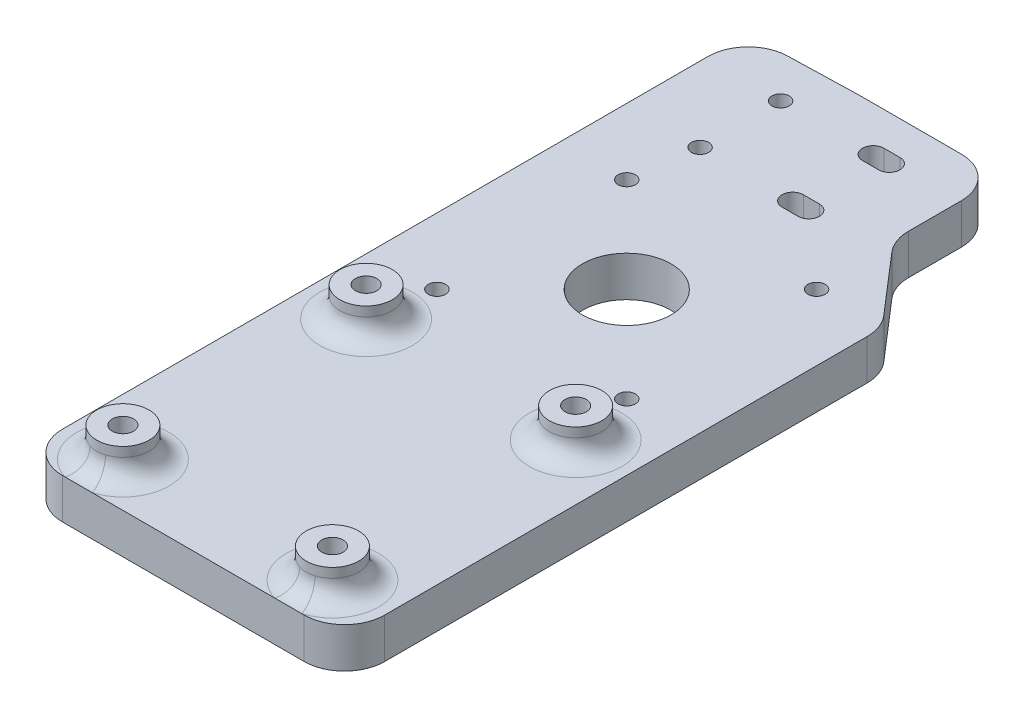
SolidWorks part; units mm, degrees
ref_plane "Alzado" through (0, 0, 0) normal (0, 0, 1) x (1, 0, 0)
ref_plane "Planta" through (0, 0, 0) normal (0, 1, 0) x (1, 0, 0)
ref_plane "Vista lateral" through (0, 0, 0) normal (1, 0, 0) x (0, 0, -1)
sketch "Croquis1" plane through (0, 0, 0) normal (0, 1, 0) x (1, 0, 0)
  line L0 (12.4888, 90.7353) -> (-12.4888, 90.7353)
  line L1 (-12.4888, 90.7353) -> (12.4888, 90.7353)
  line L2 (-40, 39.8326) -> (-40, -80)
  line L3 (-30, -90) -> (30, -90)
  line L4 (40, 39.8326) -> (40, -80)
  line L6 (0, -49) -> (-4.6306, -49) construction
  line L9 (0, 0) -> (0, -51.3503) construction
  line L10 (-40, 39.8326) -> (-40, 80.2637)
  line L11 (-30.2672, 90.2601) -> (-12.4888, 90.7353)
  line L12 (22.4888, 80.7353) -> (22.4888, 67.5648)
  line L13 (24.9172, 61.0325) -> (37.5716, 46.365)
  arc A2 (-13.023, 90.7211) -> (-12.4888, 90.7353) centre (-12.4888, 80.7353) cw
  arc A12 (-40, -80) -> (-30, -90) centre (-30, -80) ccw
  arc A13 (40, -80) -> (30, -90) centre (30, -80) cw
  arc A14 (22.4888, 80.7353) -> (12.4888, 90.7353) centre (12.4888, 80.7353) ccw
  arc A15 (22.4888, 67.5648) -> (24.9172, 61.0325) centre (32.4888, 67.5648) ccw
  arc A16 (37.5716, 46.365) -> (40, 39.8326) centre (30, 39.8326) cw
  arc A17 (-30.2672, 90.2601) -> (-40, 80.2637) centre (-30, 80.2637) ccw
  point P0 (0, 0)
  point P15 (-22.4888, 90.7353)
  point P26 (-40, -90)
  point P29 (40, -90)
  dimension "D1" = 10
  dimension "D3" = 80
extrude "Saliente-Extruir1" add sketch "Croquis1" along normal blind 10 contours A2 L2 L3 L4 L0 region at (-1.4705, 0, 3.0627)
sketch "Croquis2" plane through (0, 0, 0) normal (0, -1, 0) x (1, 0, 0)
  line L0 (-30, 90) -> (30, 90) construction
  line L1 (0, 0) -> (0, 18.1232) construction
  line L2 (-26.0188, 48.8) -> (-13.5394, 48.8) construction
  circle A0 centre (-26.0188, 79) radius 6.5
  circle A1 centre (-26.0188, 79) radius 2.65
  circle A2 centre (-26.0188, 18.6) radius 2.65
  circle A3 centre (-26.0188, 18.6) radius 6.5
  circle A4 centre (26.0188, 79) radius 2.65
  circle A5 centre (26.0188, 79) radius 6.5
  circle A6 centre (26.0188, 18.6) radius 6.5
  circle A7 centre (26.0188, 18.6) radius 2.65
  dimension "D2" = 13
  dimension "D3" = 5.3
  dimension "D1" = 11
  dimension "D4" = 30.2
extrude "Saliente-Extruir2" add sketch "Croquis2" against normal blind 7.35 from surface starting at face at (5.9415, 10, -23.6486)
sketch "Croquis3" plane through (0, 0, 0) normal (0, -1, 0) x (1, 0, 0)
  circle A0 centre (-26.0188, 79) radius 2.65
  circle A1 centre (-26.0188, 18.6) radius 2.65
  circle A2 centre (26.0188, 18.6) radius 2.65
  circle A3 centre (26.0188, 79) radius 2.65
extrude "Cortar-Extruir1" cut sketch "Croquis3" against normal blind 68 and the other way blind 46
sketch "Croquis4" plane through (0, 0, 0) normal (0, -1, 0) x (1, 0, 0)
  line L0 (0, 0) -> (0, -20.1076) construction
  line L1 (0, -20.1076) -> (-7.7372, -20.1076) construction
  circle A0 centre (-23.57, -43.6776) radius 2.15
  circle A1 centre (-23.57, 3.4624) radius 2.15
  circle A2 centre (23.57, 3.4624) radius 2.15
  circle A3 centre (23.57, -43.6776) radius 2.15
  circle A4 centre (0, -20.1076) radius 11
  dimension "D1" = 4.3
  dimension "D4" = 22
  dimension "D2" = 23.57
  dimension "D3" = 23.57
extrude "Cortar-Extruir2" cut sketch "Croquis4" against normal blind 32 and the other way blind 37
sketch "Croquis6" plane through (0, 10, 0) normal (0, 1, 0) x (1, 0, 0)
  line L0 (-23.57, 43.6776) -> (-23.57, 59.7353) construction
  line L1 (1.58, 79.7353) -> (5.58, 79.7353) construction
  line L2 (-24.1067, 69.7353) -> (-27.2294, 69.7353) construction
  line L3 (1.58, 82.3889) -> (5.58, 82.3889)
  line L6 (1.58, 77.0818) -> (5.58, 77.0818)
  line L9 (0, 0) -> (0, 19.1883) construction
  line L10 (1.58, 59.7353) -> (5.58, 59.7353) construction
  line L11 (1.58, 57.0818) -> (5.58, 57.0818)
  line L12 (1.58, 62.3889) -> (5.58, 62.3889)
  circle A9 centre (-21.42, 59.7353) radius 2.15
  circle A10 centre (-21.42, 79.7353) radius 2.15
  arc A11 (1.58, 82.3889) -> (1.58, 77.0818) centre (1.58, 79.7353) ccw
  arc A12 (5.58, 77.0818) -> (5.58, 82.3889) centre (5.58, 79.7353) ccw
  arc A13 (1.58, 57.0818) -> (1.58, 62.3889) centre (1.58, 59.7353) cw
  arc A14 (5.58, 62.3889) -> (5.58, 57.0818) centre (5.58, 59.7353) cw
  point P4 (3.58, 79.7353)
  point P13 (3.58, 59.7353)
extrude "Cortar-Extruir3" cut sketch "Croquis6" against normal blind 28 contours A9 | A10 | L6 A12 L3 A11 | L11 A14 L12 A13
fillet "Redondeo4" radius 5 4 edges at (26.0188, 10, 85.5) (-26.0188, 10, 85.5) (26.0188, 10, 25.1) (-26.0188, 10, 25.1)
hole_wizard "Refrentado para tornillo con cabeza troncocónica de M51" positions "Croquis8" profile "Croquis9" counterbore size "M5" standard "Ansi Metric" end condition through all
sketch "Croquis8" plane through (0, 0, 0) normal (0, -1, 0) x (-1, 0, 0)
  point P0 (-26.0188, -18.6)
  point P3 (-26.0188, -79)
  point P6 (26.0188, -79)
  point P9 (26.0188, -18.6)
sketch "Croquis9" plane through (26.0188, 0, 18.6) normal (1, 0, 0) x (0, 0, -1)
  line L0 (0, 0) -> (0, 17.35)
  line L1 (0, 17.35) -> (2.65, 17.35)
  line L3 (2.65, 17.35) -> (2.65, 3.7)
  line L4 (2.65, 3.7) -> (5.5, 3.7)
  line L5 (5.5, 3.7) -> (5.5, 0)
  line L7 (5.5, 0) -> (0, 0)
  line L11 (0, -6.35) -> (0, 107.95) construction
  dimension "Diámetro de taladro hasta el siguiente" = 5.3
  dimension "Profundidad de taladro hasta el siguiente" = 17.35
  dimension "Diámetro de refrentado" = 11
  dimension "Profundidad de refrentado" = 3.7
sketch "Croquis10" plane through (0, 10, 0) normal (0, 1, 0) x (1, 0, 0)
  line L0 (26.0188, -79) -> (26.0188, -81.65) construction
  line L1 (31.4125, -79) -> (31.4125, -81.65)
  line L2 (20.6251, -79) -> (20.6251, -81.65)
  circle A0 centre (26.0188, -79) radius 2.65 construction
  arc A1 (31.4125, -79) -> (20.6251, -79) centre (26.0188, -79) ccw
  arc A2 (20.6251, -81.65) -> (31.4125, -81.65) centre (26.0188, -81.65) ccw
  point P5 (26.0188, -80.325)
sketch "Croquis11" plane through (0, 0, 0) normal (0, -1, 0) x (1, 0, 0)
  line L0 (-21.9074, 36.8687) -> (-23.58, 38.144)
  line L1 (-23.58, 38.144) -> (-25.3708, 38.1161)
  line L2 (-28.4834, 53.6237) -> (-28.4834, 55.7006)
  line L3 (-28.4834, 55.7006) -> (-27.7447, 55.7006)
  line L4 (-27.7447, 55.7006) -> (-27.0061, 55.7006)
  line L5 (-27.0061, 55.7006) -> (-27.0061, 53.7308)
  line L6 (-24.4708, 50.8261) -> (-22.9433, 50.8991)
  line L7 (-22.9433, 50.8991) -> (-22.8728, 53.2999)
  line L8 (-22.8728, 53.2999) -> (-22.8023, 55.7006)
  line L9 (-22.8023, 55.7006) -> (-22.0725, 55.7006)
  line L10 (-22.0725, 55.7006) -> (-21.3428, 55.7006)
  line L11 (-21.3428, 55.7006) -> (-21.3428, 52.7424)
  line L12 (-21.3428, 52.7424) -> (-21.3428, 49.7841)
  line L13 (-21.3428, 49.7841) -> (-20.5425, 49.0561)
  line L14 (6.5529, 37.0872) -> (5.5861, 38.1856)
  line L15 (5.5861, 38.1856) -> (3.7489, 36.4168)
  line L16 (3.7085, 44.472) -> (5.4924, 42.7233)
  line L17 (5.4924, 42.7233) -> (7.2941, 44.472)
  line L18 (24.7134, 51.5147) -> (22.9786, 51.5147)
  line L19 (22.9786, 51.5147) -> (22.9786, 52.2534)
  line L20 (22.9786, 52.2534) -> (22.9786, 52.9921)
  line L21 (22.9786, 52.9921) -> (24.5962, 52.9921)
  line L22 (24.2098, 54.1001) -> (22.363, 54.1001)
  line L23 (22.363, 54.1001) -> (22.363, 52.4996)
  line L24 (22.363, 52.4996) -> (22.363, 50.8991)
  line L25 (22.363, 50.8991) -> (24.2713, 50.8272)
  line L26 (24.2713, 50.8272) -> (26.1795, 50.7553)
  line L27 (26.1795, 50.7553) -> (26.1795, 50.027)
  line L28 (26.1795, 50.027) -> (26.1795, 49.2986)
  line L29 (26.1795, 49.2986) -> (24.3206, 49.2986)
  line L30 (13.8681, 50.027) -> (13.8681, 50.7553)
  line L31 (13.8681, 50.7553) -> (15.7763, 50.8272)
  line L32 (15.7763, 50.8272) -> (17.6846, 50.8991)
  line L33 (17.6846, 50.8991) -> (17.7551, 53.2999)
  line L34 (17.7551, 53.2999) -> (17.8256, 55.7006)
  line L35 (17.8256, 55.7006) -> (18.5553, 55.7006)
  line L36 (18.5553, 55.7006) -> (19.2851, 55.7006)
  line L37 (19.2851, 55.7006) -> (19.2851, 53.0099)
  line L38 (15.9278, 49.2986) -> (13.8681, 49.2986)
  line L39 (13.8681, 49.2986) -> (13.8681, 50.027)
  line L40 (7.2199, 50.0373) -> (7.2199, 50.776)
  line L41 (7.2199, 50.776) -> (9.0174, 50.776)
  line L42 (11.4058, 53.5338) -> (11.4058, 55.7006)
  line L43 (11.4058, 55.7006) -> (12.1669, 55.7006)
  line L44 (12.1669, 55.7006) -> (12.928, 55.7006)
  line L45 (12.928, 55.7006) -> (12.844, 53.0934)
  line L46 (9.2991, 49.2986) -> (7.2199, 49.2986)
  line L47 (7.2199, 49.2986) -> (7.2199, 50.0373)
  line L48 (2.4072, 53.4845) -> (4.2651, 53.4845)
  line L49 (4.2651, 53.4845) -> (4.2651, 52.7458)
  line L50 (4.2651, 52.7458) -> (4.2651, 52.0072)
  line L51 (4.2651, 52.0072) -> (2.5244, 52.0072)
  line L52 (2.7877, 50.8991) -> (4.6345, 50.8991)
  line L53 (4.6345, 50.8991) -> (4.6345, 52.4996)
  line L54 (4.6345, 52.4996) -> (4.6345, 54.1001)
  line L55 (4.6345, 54.1001) -> (2.9724, 54.1729)
  line L56 (2.9724, 54.1729) -> (1.3104, 54.2457)
  line L57 (1.3104, 54.2457) -> (1.3104, 54.9992)
  line L58 (1.3104, 54.9992) -> (1.3104, 55.7527)
  line L59 (1.3104, 55.7527) -> (3.3043, 55.6622)
  line L60 (-7.3077, 50.027) -> (-7.3077, 50.7553)
  line L61 (-7.3077, 50.7553) -> (-5.3994, 50.8272)
  line L62 (-5.3994, 50.8272) -> (-3.4911, 50.8991)
  line L63 (-3.4911, 50.8991) -> (-3.4207, 53.2999)
  line L64 (-3.4207, 53.2999) -> (-3.3502, 55.7006)
  line L65 (-3.3502, 55.7006) -> (-2.6204, 55.7006)
  line L66 (-2.6204, 55.7006) -> (-1.8906, 55.7006)
  line L67 (-1.8906, 55.7006) -> (-1.8906, 53.0099)
  line L68 (-5.2479, 49.2986) -> (-7.3077, 49.2986)
  line L69 (-7.3077, 49.2986) -> (-7.3077, 50.027)
  line L70 (-10.6206, 51.5147) -> (-12.4785, 51.5147)
  line L71 (-12.4785, 51.5147) -> (-12.4785, 52.2534)
  line L72 (-12.4785, 52.2534) -> (-12.4785, 52.9921)
  line L73 (-12.4785, 52.9921) -> (-10.7378, 52.9921)
  line L74 (-10.8694, 50.776) -> (-9.0313, 50.776)
  line L75 (-9.0313, 50.776) -> (-9.0313, 50.0373)
  line L76 (-9.0313, 50.0373) -> (-9.0313, 49.2986)
  line L77 (-9.0313, 49.2986) -> (-11.1355, 49.2986)
  line L78 (-19.8654, 52.4996) -> (-19.8654, 55.7006)
  line L79 (-19.8654, 55.7006) -> (-19.1267, 55.7006)
  line L80 (-19.1267, 55.7006) -> (-18.388, 55.7006)
  line L81 (-18.388, 55.7006) -> (-18.388, 52.4996)
  line L82 (-18.388, 52.4996) -> (-18.388, 49.2986)
  line L83 (-18.388, 49.2986) -> (-19.1267, 49.2986)
  line L84 (-19.1267, 49.2986) -> (-19.8654, 49.2986)
  line L85 (-19.8654, 49.2986) -> (-19.8654, 52.4996)
  line L86 (35.5363, 51.5058) -> (35.5363, 54.2232)
  line L87 (35.5363, 54.2232) -> (32.8277, 54.2232)
  line L88 (32.8277, 54.2232) -> (30.1192, 54.2232)
  line L89 (30.1192, 54.2232) -> (30.1192, 53.5338)
  line L90 (32.7539, 52.2534) -> (34.7976, 52.2534)
  line L91 (34.7976, 52.2534) -> (34.7976, 51.5425)
  line L92 (33.1356, 48.8588) -> (35.5363, 48.7883)
  line L93 (35.5363, 48.7883) -> (35.5363, 51.5058)
  arc A0 (-21.7929, 32.6977) -> (-21.8352, 32.5543) centre (-21.5714, 32.5543) ccw
  arc A1 (-21.5762, 33.0144) -> (-21.7929, 32.6977) centre (-15.4233, 28.5729) ccw
  arc A2 (-21.2912, 33.3841) -> (-21.5762, 33.0144) centre (-15.5733, 28.6812) ccw
  arc A3 (-20.9535, 33.7758) -> (-21.2912, 33.3841) centre (-12.6842, 26.305) ccw
  arc A4 (-20.9535, 33.7758) -> (-20.6219, 34.1803) centre (-24.9909, 37.4233) ccw
  arc A5 (-20.6219, 34.1803) -> (-20.3547, 34.5887) centre (-23.9371, 36.6411) ccw
  arc A6 (-20.3547, 34.5887) -> (-20.1765, 34.9489) centre (-23.2212, 36.2309) ccw
  arc A7 (-20.1765, 34.9489) -> (-20.1533, 35.1726) centre (-20.5331, 35.099) ccw
  arc A8 (-20.1533, 35.1726) -> (-20.2693, 35.4017) centre (-20.6135, 35.0834) ccw
  arc A9 (-20.2693, 35.4017) -> (-20.7022, 35.8444) centre (-28.3805, 27.9036) ccw
  arc A10 (-20.7022, 35.8444) -> (-21.2608, 36.3495) centre (-28.5249, 27.7542) ccw
  arc A11 (-21.2608, 36.3495) -> (-21.9074, 36.8687) centre (-31.9176, 23.7397) ccw
  arc A12 (-25.3708, 38.1161) -> (-26.6444, 38.0299) centre (-25.1791, 25.8317) ccw
  arc A13 (-26.6444, 38.0299) -> (-27.5051, 37.7963) centre (-26.2775, 34.9755) ccw
  arc A14 (-27.5051, 37.7963) -> (-28.3226, 37.3077) centre (-26.0188, 34.3811) ccw
  arc A15 (-28.3226, 37.3077) -> (-29.4886, 36.3239) centre (-14.4056, 19.6288) ccw
  arc A16 (-29.4886, 36.3239) -> (-29.8579, 35.9562) centre (-25.8949, 32.3461) ccw
  arc A17 (-29.8579, 35.9562) -> (-30.1699, 35.572) centre (-26.6312, 33.0169) ccw
  arc A18 (-30.1699, 35.572) -> (-30.3922, 35.2229) centre (-27.2951, 33.4962) ccw
  arc A19 (-30.3922, 35.2229) -> (-30.4533, 34.988) centre (-29.971, 34.988) ccw
  arc A20 (-30.4533, 34.988) -> (-30.3913, 34.7523) centre (-29.9738, 34.988) ccw
  arc A21 (-30.3913, 34.7523) -> (-30.164, 34.3986) centre (-27.2015, 36.5531) ccw
  arc A22 (-30.164, 34.3986) -> (-29.8454, 34.0085) centre (-26.5246, 37.0454) ccw
  arc A23 (-29.8454, 34.0085) -> (-29.4684, 33.6338) centre (-25.7278, 37.7741) ccw
  arc A24 (-29.0911, 33.2766) -> (-29.4684, 33.6338) centre (-36.9497, 25.3528) ccw
  arc A25 (-28.7728, 32.9395) -> (-29.0911, 33.2766) centre (-34.0818, 28.2444) ccw
  arc A26 (-28.5286, 32.6491) -> (-28.7728, 32.9395) centre (-34.416, 27.9489) ccw
  arc A27 (-28.4834, 32.52) -> (-28.5286, 32.6491) centre (-28.6902, 32.52) ccw
  arc A28 (-28.6329, 32.4158) -> (-28.4834, 32.52) centre (-28.5945, 32.52) ccw
  arc A29 (-29.1844, 32.6662) -> (-28.6329, 32.4158) centre (-27.1979, 36.3089) ccw
  arc A30 (-29.8159, 33.0694) -> (-29.1844, 32.6662) centre (-26.5815, 37.4392) ccw
  arc A31 (-30.3073, 33.5147) -> (-29.8159, 33.0694) centre (-27.8204, 35.7654) ccw
  arc A32 (-30.3073, 33.5147) -> (-30.5256, 33.7128) centre (-31.4223, 32.5057) ccw
  arc A33 (-30.5256, 33.7128) -> (-30.7934, 33.8803) centre (-31.7051, 32.125) ccw
  arc A34 (-30.7934, 33.8803) -> (-31.0678, 33.9951) centre (-31.621, 32.2869) ccw
  arc A35 (-31.0678, 33.9951) -> (-31.304, 34.0324) centre (-31.304, 33.2657) ccw
  arc A36 (-31.7288, 34.1047) -> (-31.304, 34.0324) centre (-31.304, 35.3167) ccw
  arc A37 (-32.0923, 34.3129) -> (-31.7288, 34.1047) centre (-31.3483, 35.1904) ccw
  arc A38 (-32.3366, 34.6215) -> (-32.0923, 34.3129) centre (-31.4448, 35.0766) ccw
  arc A39 (-32.4231, 34.9813) -> (-32.3366, 34.6215) centre (-31.6316, 34.9813) ccw
  arc A40 (-32.4231, 34.9813) -> (-32.4814, 35.1754) centre (-32.7757, 34.9813) ccw
  arc A41 (-32.4814, 35.1754) -> (-32.7305, 35.5219) centre (-36.8916, 32.2669) ccw
  arc A42 (-32.7305, 35.5219) -> (-33.0689, 35.9177) centre (-37.4441, 31.8347) ccw
  arc A43 (-33.0689, 35.9177) -> (-33.4696, 36.3191) centre (-39.2224, 30.1753) ccw
  arc A44 (-34.2263, 37.1004) -> (-33.4696, 36.3191) centre (-25.8639, 44.4417) ccw
  arc A45 (-34.1987, 37.4176) -> (-34.2263, 37.1004) centre (-34.0606, 37.2458) ccw
  arc A46 (-33.8228, 37.4345) -> (-34.1987, 37.4176) centre (-33.9992, 37.1694) ccw
  arc A47 (-32.9118, 36.7675) -> (-33.8228, 37.4345) centre (-40.787, 26.9679) ccw
  arc A48 (-32.9118, 36.7675) -> (-32.5122, 36.4746) centre (-29.4133, 41.1209) ccw
  arc A49 (-32.5122, 36.4746) -> (-32.0991, 36.227) centre (-29.7454, 40.6231) ccw
  arc A50 (-32.0991, 36.227) -> (-31.7278, 36.0511) centre (-30.1248, 39.9144) ccw
  arc A51 (-31.7278, 36.0511) -> (-31.4825, 36.0022) centre (-31.4825, 36.6421) ccw
  arc A52 (-31.4825, 36.0022) -> (-31.0911, 36.1465) centre (-31.4825, 36.6052) ccw
  arc A53 (-31.0911, 36.1465) -> (-30.4077, 36.7828) centre (-38.1198, 44.3825) ccw
  arc A54 (-30.4077, 36.7828) -> (-29.5542, 37.7226) centre (-41.4864, 47.7001) ccw
  arc A55 (-29.5542, 37.7226) -> (-28.5152, 39.0134) centre (-63.5871, 66.1803) ccw
  arc A56 (-28.5152, 39.0134) -> (-28.3768, 39.2937) centre (-29.1364, 39.4946) ccw
  arc A57 (-28.3768, 39.2937) -> (-28.274, 39.786) centre (-32.9762, 40.5102) ccw
  arc A58 (-28.274, 39.786) -> (-28.2072, 40.4153) centre (-34.938, 40.8123) ccw
  arc A59 (-28.2072, 40.4153) -> (-28.1854, 41.1551) centre (-40.7482, 41.1551) ccw
  arc A60 (-28.1854, 41.1551) -> (-28.2106, 42.0676) centre (-44.6696, 41.1551) ccw
  arc A61 (-28.2106, 42.0676) -> (-28.2961, 42.6915) centre (-32.1105, 41.8514) ccw
  arc A62 (-28.2961, 42.6915) -> (-28.4633, 43.191) centre (-30.7199, 42.1577) ccw
  arc A63 (-28.4633, 43.191) -> (-28.7424, 43.684) centre (-31.4758, 41.8116) ccw
  arc A64 (-28.7424, 43.684) -> (-29.4471, 44.613) centre (-38.6834, 36.8741) ccw
  arc A65 (-29.4471, 44.613) -> (-30.2534, 45.4912) centre (-39.5355, 36.1601) ccw
  arc A66 (-30.2534, 45.4912) -> (-31.0141, 46.1948) centre (-40.3014, 35.3902) ccw
  arc A67 (-31.0141, 46.1948) -> (-31.4162, 46.3439) centre (-31.4162, 45.727) ccw
  arc A68 (-31.4162, 46.3439) -> (-31.6139, 46.2915) centre (-31.4162, 45.9445) ccw
  arc A69 (-31.6139, 46.2915) -> (-31.9456, 46.0825) centre (-29.4339, 42.4643) ccw
  arc A70 (-31.9456, 46.0825) -> (-32.322, 45.7947) centre (-29.0035, 41.8443) ccw
  arc A71 (-32.322, 45.7947) -> (-32.698, 45.4541) centre (-27.9588, 40.6006) ccw
  arc A72 (-33.5492, 44.6913) -> (-32.698, 45.4541) centre (-42.022, 55.0027) ccw
  arc A73 (-33.923, 44.6687) -> (-33.5492, 44.6913) centre (-33.7517, 44.9378) ccw
  arc A74 (-33.979, 44.9742) -> (-33.923, 44.6687) centre (-33.8093, 44.8474) ccw
  arc A75 (-33.28, 45.8245) -> (-33.979, 44.9742) centre (-24.52, 37.9104) ccw
  arc A76 (-33.28, 45.8245) -> (-32.9132, 46.2639) centre (-38.713, 50.7328) ccw
  arc A77 (-32.9132, 46.2639) -> (-32.5974, 46.7134) centre (-37.8343, 50.0558) ccw
  arc A78 (-32.5974, 46.7134) -> (-32.3652, 47.1152) centre (-37.0405, 49.5491) ccw
  arc A79 (-32.3652, 47.1152) -> (-32.2923, 47.3719) centre (-32.9517, 47.4205) ccw
  arc A80 (-32.1907, 47.7326) -> (-32.2923, 47.3719) centre (-31.3562, 47.303) ccw
  arc A81 (-31.9546, 48.0347) -> (-32.1907, 47.7326) centre (-31.2784, 47.2629) ccw
  arc A82 (-31.6161, 48.2367) -> (-31.9546, 48.0347) centre (-31.2354, 47.2139) ccw
  arc A83 (-31.2218, 48.3099) -> (-31.6161, 48.2367) centre (-31.2088, 47.1425) ccw
  arc A84 (-31.2218, 48.3099) -> (-31.034, 48.3614) centre (-31.2261, 48.6938) ccw
  arc A85 (-31.034, 48.3614) -> (-30.6881, 48.5782) centre (-33.899, 53.3183) ccw
  arc A86 (-30.6881, 48.5782) -> (-30.2896, 48.8713) centre (-34.2528, 53.8407) ccw
  arc A87 (-30.2896, 48.8713) -> (-29.8816, 49.2178) centre (-35.7187, 55.6787) ccw
  arc A88 (-29.0655, 49.8825) -> (-29.8816, 49.2178) centre (-22.9875, 41.5868) ccw
  arc A89 (-28.777, 49.8133) -> (-29.0655, 49.8825) centre (-28.9506, 49.7256) ccw
  arc A90 (-28.8193, 49.4223) -> (-28.777, 49.8133) centre (-29.0991, 49.6504) ccw
  arc A91 (-29.5635, 48.5886) -> (-28.8193, 49.4223) centre (-38.4938, 57.3088) ccw
  arc A92 (-29.5635, 48.5886) -> (-29.9042, 48.2199) centre (-23.0365, 42.2152) ccw
  arc A93 (-29.9042, 48.2199) -> (-30.1919, 47.8655) centre (-25.2096, 44.1152) ccw
  arc A94 (-30.1919, 47.8655) -> (-30.4074, 47.5595) centre (-25.4469, 44.2939) ccw
  arc A95 (-30.4074, 47.5595) -> (-30.4533, 47.4065) centre (-30.1749, 47.4065) ccw
  arc A96 (-30.4533, 47.4065) -> (-30.3114, 47.0674) centre (-29.9771, 47.4065) ccw
  arc A97 (-30.3114, 47.0674) -> (-28.9834, 45.7803) centre (45.816, 124.2859) ccw
  arc A98 (-28.9834, 45.7803) -> (-27.6494, 44.535) centre (32.7732, 110.5969) ccw
  arc A99 (-27.6494, 44.535) -> (-27.2383, 44.3433) centre (-27.1388, 45.0932) ccw
  arc A100 (-27.2383, 44.3433) -> (-26.2266, 44.2672) centre (-26.0621, 53.2161) ccw
  arc A101 (-26.2266, 44.2672) -> (-24.8209, 44.2722) centre (-25.6388, 76.2426) ccw
  arc A102 (-24.8209, 44.2722) -> (-23.4378, 44.3275) centre (-26.0494, 92.2956) ccw
  arc A103 (-23.4378, 44.3275) -> (-22.9585, 44.4527) centre (-23.5052, 45.5656) ccw
  arc A104 (-22.9585, 44.4527) -> (-22.2404, 44.9291) centre (-24.4343, 47.457) ccw
  arc A105 (-22.2404, 44.9291) -> (-21.2322, 45.8668) centre (-35.3656, 60.0521) ccw
  arc A106 (-21.2322, 45.8668) -> (-20.2769, 46.8637) centre (-42.2823, 66.9942) ccw
  arc A107 (-20.2769, 46.8637) -> (-20.1116, 47.2892) centre (-20.742, 47.2892) ccw
  arc A108 (-20.1116, 47.2892) -> (-20.1604, 47.4889) centre (-20.5447, 47.2892) ccw
  arc A109 (-20.1604, 47.4889) -> (-20.3428, 47.8) centre (-23.2915, 45.8621) ccw
  arc A110 (-20.3428, 47.8) -> (-20.5974, 48.1475) centre (-23.8936, 45.4663) ccw
  arc A111 (-20.5974, 48.1475) -> (-20.8986, 48.4867) centre (-24.6476, 44.853) ccw
  arc A112 (-20.8986, 48.4867) -> (-21.4421, 48.9762) centre (-24.7732, 44.7312) ccw
  arc A113 (-21.4421, 48.9762) -> (-21.8851, 49.1953) centre (-22.1879, 48.0258) ccw
  arc A114 (-21.8851, 49.1953) -> (-22.5084, 49.2819) centre (-22.5705, 46.5481) ccw
  arc A115 (-22.5084, 49.2819) -> (-24.038, 49.2995) centre (-24.0649, -19.2388) ccw
  arc A116 (-25.2957, 49.3209) -> (-24.038, 49.2995) centre (-24.0232, 87.1927) ccw
  arc A117 (-26.0898, 49.3959) -> (-25.2957, 49.3209) centre (-25.0744, 55.908) ccw
  arc A118 (-26.6735, 49.5433) -> (-26.0898, 49.3959) centre (-25.5887, 52.6093) ccw
  arc A119 (-27.1969, 49.7921) -> (-26.6735, 49.5433) centre (-25.7401, 52.1814) ccw
  arc A120 (-27.8498, 50.34) -> (-27.1969, 49.7921) centre (-25.7183, 52.2171) ccw
  arc A121 (-28.2365, 51.0108) -> (-27.8498, 50.34) centre (-26.3805, 51.634) ccw
  arc A122 (-28.4301, 51.9927) -> (-28.2365, 51.0108) centre (-24.5573, 52.2462) ccw
  arc A123 (-28.4834, 53.6237) -> (-28.4301, 51.9927) centre (-3.5103, 53.6237) ccw
  arc A124 (-27.0061, 53.7308) -> (-26.9147, 52.0665) centre (-11.7975, 53.7308) ccw
  arc A125 (-26.9147, 52.0665) -> (-26.5601, 51.2585) centre (-25.4496, 52.2278) ccw
  arc A126 (-26.5601, 51.2585) -> (-25.8469, 50.8791) centre (-25.7059, 52.0041) ccw
  arc A127 (-25.8469, 50.8791) -> (-24.4708, 50.8261) centre (-24.8524, 58.8109) ccw
  arc A128 (-20.5425, 49.0561) -> (-20.1991, 48.777) centre (-17.8665, 51.9977) ccw
  arc A129 (-20.1991, 48.777) -> (-19.8291, 48.5399) centre (-17.9318, 51.9076) ccw
  arc A130 (-19.8291, 48.5399) -> (-19.4856, 48.3723) centre (-18.2464, 51.3492) ccw
  arc A131 (-19.4856, 48.3723) -> (-19.2375, 48.3209) centre (-19.2279, 48.9912) ccw
  arc A132 (-18.8102, 48.2394) -> (-19.2375, 48.3209) centre (-19.2554, 47.0672) ccw
  arc A133 (-18.4564, 48.0178) -> (-18.8102, 48.2394) centre (-19.1901, 47.2391) ccw
  arc A134 (-18.2238, 47.6858) -> (-18.4564, 48.0178) centre (-19.1424, 47.2898) ccw
  arc A135 (-18.1418, 47.2884) -> (-18.2238, 47.6858) centre (-19.1456, 47.2884) ccw
  arc A136 (-18.1418, 47.2884) -> (-18.0791, 47.0613) centre (-17.6992, 47.2884) ccw
  arc A137 (-18.0791, 47.0613) -> (-17.8348, 46.6954) centre (-14.2703, 49.3389) ccw
  arc A138 (-17.8348, 46.6954) -> (-17.4969, 46.2844) centre (-13.5676, 49.86) ccw
  arc A139 (-17.4969, 46.2844) -> (-17.0968, 45.8793) centre (-12.3509, 50.9672) ccw
  arc A140 (-16.7084, 45.4934) -> (-17.0968, 45.8793) centre (-22.9939, 39.5574) ccw
  arc A141 (-16.4088, 45.1409) -> (-16.7084, 45.4934) centre (-19.9307, 42.4503) ccw
  arc A142 (-16.2086, 44.8507) -> (-16.4088, 45.1409) centre (-19.2989, 42.9329) ccw
  arc A143 (-16.222, 44.7343) -> (-16.2086, 44.8507) centre (-16.2887, 44.801) ccw
  arc A144 (-16.5071, 44.6876) -> (-16.222, 44.7343) centre (-16.3971, 44.9094) ccw
  arc A145 (-17.2428, 45.0967) -> (-16.5071, 44.6876) centre (-12.5228, 52.7186) ccw
  arc A146 (-17.9449, 45.5886) -> (-17.2428, 45.0967) centre (-13.2572, 51.5327) ccw
  arc A147 (-18.2327, 45.9795) -> (-17.9449, 45.5886) centre (-17.3779, 46.3075) ccw
  arc A148 (-18.2327, 45.9795) -> (-18.5122, 46.2694) centre (-18.7147, 45.7946) ccw
  arc A149 (-18.5122, 46.2694) -> (-18.9387, 46.2948) centre (-18.7609, 45.6862) ccw
  arc A150 (-18.9387, 46.2948) -> (-19.5016, 46.0065) centre (-18.4669, 44.6798) ccw
  arc A151 (-19.5016, 46.0065) -> (-20.1461, 45.4205) centre (-15.9494, 41.452) ccw
  arc A152 (-20.1461, 45.4205) -> (-21.205, 44.2155) centre (-4.1973, 30.3389) ccw
  arc A153 (-21.205, 44.2155) -> (-21.7643, 43.3275) centre (-17.8725, 41.4965) ccw
  arc A154 (-21.7643, 43.3275) -> (-22.0485, 42.4024) centre (-18.662, 41.8679) ccw
  arc A155 (-22.0485, 42.4024) -> (-22.1718, 41.1148) centre (-11.5788, 40.7501) ccw
  arc A156 (-22.1718, 41.1148) -> (-22.1835, 40.0963) centre (-0.0103, 40.3517) ccw
  arc A157 (-22.1835, 40.0963) -> (-22.1179, 39.4866) centre (-18.9712, 40.1333) ccw
  arc A158 (-22.1179, 39.4866) -> (-21.9495, 39.0024) centre (-20.2114, 39.8784) ccw
  arc A159 (-21.9495, 39.0024) -> (-21.6271, 38.4645) centre (-18.1171, 40.9339) ccw
  arc A160 (-21.6271, 38.4645) -> (-20.8727, 37.4751) centre (-8.3612, 47.7975) ccw
  arc A161 (-20.8727, 37.4751) -> (-20.1415, 36.6891) centre (-13.9101, 43.2194) ccw
  arc A162 (-20.1415, 36.6891) -> (-19.4951, 36.1486) centre (-15.6977, 41.3462) ccw
  arc A163 (-19.4951, 36.1486) -> (-19.0467, 36.0022) centre (-19.0467, 36.7623) ccw
  arc A164 (-19.0467, 36.0022) -> (-18.7999, 36.0586) centre (-19.0467, 36.57) ccw
  arc A165 (-18.7999, 36.0586) -> (-18.4167, 36.2678) centre (-20.7024, 40.0009) ccw
  arc A166 (-18.4167, 36.2678) -> (-17.9882, 36.5602) centre (-21.1569, 40.7433) ccw
  arc A167 (-17.9882, 36.5602) -> (-17.5701, 36.9063) centre (-21.781, 41.5672) ccw
  arc A168 (-16.754, 37.571) -> (-17.5701, 36.9063) centre (-10.676, 29.2753) ccw
  arc A169 (-16.4655, 37.5019) -> (-16.754, 37.571) centre (-16.6391, 37.4141) ccw
  arc A170 (-16.5078, 37.1108) -> (-16.4655, 37.5019) centre (-16.7876, 37.3389) ccw
  arc A171 (-17.252, 36.2771) -> (-16.5078, 37.1108) centre (-26.1823, 44.9974) ccw
  arc A172 (-17.252, 36.2771) -> (-17.5927, 35.901) centre (-12.4075, 31.5466) ccw
  arc A173 (-17.5927, 35.901) -> (-17.8804, 35.5245) centre (-13.646, 32.5867) ccw
  arc A174 (-17.8804, 35.5245) -> (-18.0894, 35.1926) centre (-14.2671, 33.0176) ccw
  arc A175 (-18.0894, 35.1926) -> (-18.1418, 34.9946) centre (-17.7415, 34.9946) ccw
  arc A176 (-18.2251, 34.6349) -> (-18.1418, 34.9946) centre (-18.9598, 34.9946) ccw
  arc A177 (-18.4616, 34.3211) -> (-18.2251, 34.6349) centre (-19.1567, 35.091) ccw
  arc A178 (-18.809, 34.1071) -> (-18.4616, 34.3211) centre (-19.2168, 35.1577) ccw
  arc A179 (-19.2077, 34.0324) -> (-18.809, 34.1071) centre (-19.2077, 35.1341) ccw
  arc A180 (-19.2077, 34.0324) -> (-19.4518, 33.9779) centre (-19.2077, 33.4585) ccw
  arc A181 (-19.4518, 33.9779) -> (-19.8233, 33.7792) centre (-17.7185, 30.2896) ccw
  arc A182 (-19.8233, 33.7792) -> (-20.2365, 33.5005) centre (-17.2902, 29.5795) ccw
  arc A183 (-20.2365, 33.5005) -> (-20.6365, 33.1706) centre (-16.7865, 28.9091) ccw
  arc A184 (-21.3047, 32.5813) -> (-20.6365, 33.1706) centre (-45.5852, 60.7858) ccw
  arc A185 (-21.6151, 32.3722) -> (-21.3047, 32.5813) centre (-22.3422, 33.7865) ccw
  arc A186 (-21.7636, 32.392) -> (-21.6151, 32.3722) centre (-21.6751, 32.4889) ccw
  arc A187 (-21.8352, 32.5543) -> (-21.7636, 32.392) centre (-21.6155, 32.5543) ccw
  arc A188 (10.5051, 33.9911) -> (11.7222, 33.4439) centre (13.899, 39.9129) ccw
  arc A189 (9.0565, 34.9138) -> (10.5051, 33.9911) centre (19.6399, 49.93) ccw
  arc A190 (7.651, 36.0054) -> (9.0565, 34.9138) centre (20.1031, 50.5873) ccw
  arc A191 (6.5529, 37.0872) -> (7.651, 36.0054) centre (14.6949, 44.2541) ccw
  arc A192 (1.964, 34.8644) -> (3.7489, 36.4168) centre (-12.4721, 53.2647) ccw
  arc A193 (0.4023, 33.8846) -> (1.964, 34.8644) centre (-3.4674, 41.7873) ccw
  arc A194 (-1.1472, 33.3516) -> (0.4023, 33.8846) centre (-2.51, 39.832) ccw
  arc A195 (-2.8756, 33.173) -> (-1.1472, 33.3516) centre (-2.8645, 41.518) ccw
  arc A196 (-3.9235, 33.2041) -> (-2.8756, 33.173) centre (-2.8511, 51.6838) ccw
  arc A197 (-4.6313, 33.306) -> (-3.9235, 33.2041) centre (-3.6797, 37.4048) ccw
  arc A198 (-5.2674, 33.5192) -> (-4.6313, 33.306) centre (-3.8327, 36.7459) ccw
  arc A199 (-6.0574, 33.9117) -> (-5.2674, 33.5192) centre (-1.0763, 42.945) ccw
  arc A200 (-7.139, 34.6572) -> (-6.0574, 33.9117) centre (-2.8677, 39.6964) ccw
  arc A201 (-8.1735, 35.675) -> (-7.139, 34.6572) centre (-0.8, 42.1358) ccw
  arc A202 (-9.0264, 36.8101) -> (-8.1735, 35.675) centre (-1.0611, 41.9069) ccw
  arc A203 (-9.5582, 37.907) -> (-9.0264, 36.8101) centre (-4.6601, 39.604) ccw
  arc A204 (-9.6823, 38.3806) -> (-9.5582, 37.907) centre (-6.558, 38.9465) ccw
  arc A205 (-9.787, 39.0679) -> (-9.6823, 38.3806) centre (2.5287, 40.5922) ccw
  arc A206 (-9.86, 39.8296) -> (-9.787, 39.0679) centre (3.9788, 40.7716) ccw
  arc A207 (-9.8862, 40.5575) -> (-9.86, 39.8296) centre (1.5027, 40.6031) ccw
  arc A208 (-9.624, 42.5931) -> (-9.8862, 40.5575) centre (-2.0957, 40.5887) ccw
  arc A209 (-8.8401, 44.3948) -> (-9.624, 42.5931) centre (-3.2778, 40.9034) ccw
  arc A210 (-7.5398, 45.9161) -> (-8.8401, 44.3948) centre (-3.0423, 40.7556) ccw
  arc A211 (-5.7619, 47.1281) -> (-7.5398, 45.9161) centre (-1.562, 39.0571) ccw
  arc A212 (-5.1617, 47.3893) -> (-5.7619, 47.1281) centre (-3.5812, 42.9374) ccw
  arc A213 (-4.5494, 47.5555) -> (-5.1617, 47.3893) centre (-3.766, 43.4579) ccw
  arc A214 (-3.8269, 47.647) -> (-4.5494, 47.5555) centre (-3.4608, 41.8615) ccw
  arc A215 (-2.8756, 47.6799) -> (-3.8269, 47.647) centre (-2.7784, 31.0767) ccw
  arc A216 (-1.1354, 47.5088) -> (-2.8756, 47.6799) centre (-2.8262, 39.2462) ccw
  arc A217 (0.4165, 46.9814) -> (-1.1354, 47.5088) centre (-2.4453, 41.1076) ccw
  arc A218 (1.9641, 46.0087) -> (0.4165, 46.9814) centre (-3.3055, 39.3419) ccw
  arc A219 (3.7085, 44.472) -> (1.9641, 46.0087) centre (-11.5711, 28.8849) ccw
  arc A220 (9.0487, 46.0066) -> (7.2941, 44.472) centre (22.9462, 28.3459) ccw
  arc A221 (10.5958, 46.9782) -> (9.0487, 46.0066) centre (14.3916, 39.2168) ccw
  arc A222 (12.14, 47.5083) -> (10.5958, 46.9782) centre (13.4911, 41.0582) ccw
  arc A223 (13.8681, 47.6872) -> (12.14, 47.5083) centre (13.866, 39.2682) ccw
  arc A224 (15.2694, 47.5883) -> (13.8681, 47.6872) centre (13.8656, 37.6709) ccw
  arc A225 (16.4208, 47.288) -> (15.2694, 47.5883) centre (14.5398, 42.4339) ccw
  arc A226 (17.4926, 46.7279) -> (16.4208, 47.288) centre (14.4636, 42.2371) ccw
  arc A227 (18.6528, 45.8331) -> (17.4926, 46.7279) centre (11.0435, 37.1666) ccw
  arc A228 (19.8075, 44.4106) -> (18.6528, 45.8331) centre (15.0468, 41.726) ccw
  arc A229 (20.6205, 42.4833) -> (19.8075, 44.4106) centre (11.8167, 39.9045) ccw
  arc A230 (20.9794, 40.4088) -> (20.6205, 42.4833) centre (11.7146, 39.8745) ccw
  arc A231 (20.7865, 38.5489) -> (20.9794, 40.4088) centre (15.1538, 40.0729) ccw
  arc A232 (20.0732, 36.9106) -> (20.7865, 38.5489) centre (14.8759, 40.1481) ccw
  arc A233 (18.8423, 35.3304) -> (20.0732, 36.9106) centre (11.9367, 41.9789) ccw
  arc A234 (17.3222, 34.0526) -> (18.8423, 35.3304) centre (12.0403, 41.8792) ccw
  arc A235 (15.7481, 33.3156) -> (17.3222, 34.0526) centre (14.1889, 38.6954) ccw
  arc A236 (14.796, 33.1266) -> (15.7481, 33.3156) centre (14.1767, 38.7376) ccw
  arc A237 (13.7606, 33.0861) -> (14.796, 33.1266) centre (13.9936, 40.3966) ccw
  arc A238 (12.7125, 33.1931) -> (13.7606, 33.0861) centre (14.0011, 40.6318) ccw
  arc A239 (11.7222, 33.4439) -> (12.7125, 33.1931) centre (13.8528, 39.7758) ccw
  arc A240 (29.2853, 48.5354) -> (29.5483, 48.1223) centre (32.2041, 50.1033) ccw
  arc A241 (29.1765, 48.8755) -> (29.2853, 48.5354) centre (30.1482, 48.9989) ccw
  arc A242 (29.1832, 49.2817) -> (29.1765, 48.8755) centre (30.5904, 49.0551) ccw
  arc A243 (29.3151, 49.9587) -> (29.1832, 49.2817) centre (39.6161, 47.6015) ccw
  arc A244 (29.3151, 49.9587) -> (29.4463, 50.6276) centre (18.693, 52.3894) ccw
  arc A245 (29.4463, 50.6276) -> (29.4558, 51.0274) centre (28.0175, 50.8617) ccw
  arc A246 (29.4558, 51.0274) -> (29.3544, 51.3514) centre (28.5564, 50.9238) ccw
  arc A247 (29.3544, 51.3514) -> (29.1119, 51.7223) centre (27.1151, 50.1516) ccw
  arc A248 (28.7431, 52.4876) -> (29.1119, 51.7223) centre (30.6588, 52.9391) ccw
  arc A249 (28.6255, 53.5286) -> (28.7431, 52.4876) centre (33.0397, 53.5002) ccw
  arc A250 (28.7548, 54.54) -> (28.6255, 53.5286) centre (32.8606, 53.5013) ccw
  arc A251 (29.1343, 55.2081) -> (28.7548, 54.54) centre (30.1572, 54.1852) ccw
  arc A252 (29.5421, 55.4776) -> (29.1343, 55.2081) centre (29.9974, 54.345) ccw
  arc A253 (30.0952, 55.6212) -> (29.5421, 55.4776) centre (30.376, 53.4034) ccw
  arc A254 (31.0232, 55.6863) -> (30.0952, 55.6212) centre (31.142, 47.3517) ccw
  arc A255 (33.0247, 55.7006) -> (31.0232, 55.6863) centre (33.0246, -84.7791) ccw
  arc A256 (34.5686, 55.6839) -> (33.0247, 55.7006) centre (33.0247, -15.807) ccw
  arc A257 (35.6639, 55.6283) -> (34.5686, 55.6839) centre (34.1619, 36.8526) ccw
  arc A258 (36.4415, 55.5429) -> (35.6639, 55.6283) centre (34.6087, 42.4381) ccw
  arc A259 (36.7182, 55.4051) -> (36.4415, 55.5429) centre (36.3742, 55.0611) ccw
  arc A260 (36.9449, 54.878) -> (36.7182, 55.4051) centre (36.17, 54.857) ccw
  arc A261 (37.0185, 51.442) -> (36.9449, 54.878) centre (-265.5895, 46.6774) ccw
  arc A262 (37.0538, 47.9989) -> (37.0185, 51.442) centre (-275.0593, 46.528) ccw
  arc A263 (36.8429, 47.4863) -> (37.0538, 47.9989) centre (36.3337, 47.9955) ccw
  arc A264 (36.6903, 47.4193) -> (36.8429, 47.4863) centre (36.6807, 47.6485) ccw
  arc A265 (35.7494, 47.3857) -> (36.6903, 47.4193) centre (33.5343, 122.5796) ccw
  arc A266 (34.6419, 47.3699) -> (35.7494, 47.3857) centre (34.6757, 83.8302) ccw
  arc A267 (33.3602, 47.3837) -> (34.6419, 47.3699) centre (34.7024, 112.5684) ccw
  arc A268 (31.1928, 47.441) -> (33.3602, 47.3837) centre (37.1803, 232.9124) ccw
  arc A269 (30.4086, 47.5291) -> (31.1928, 47.441) centre (31.353, 52.4031) ccw
  arc A270 (29.95, 47.7272) -> (30.4086, 47.5291) centre (30.6299, 48.6711) ccw
  arc A271 (29.5483, 48.1223) -> (29.95, 47.7272) centre (31.0314, 49.2286) ccw
  arc A272 (21.22, 50.0433) -> (21.765, 49.6589) centre (22.8862, 51.8269) ccw
  arc A273 (20.9272, 50.499) -> (21.22, 50.0433) centre (21.9726, 50.8489) ccw
  arc A274 (20.7941, 51.2159) -> (20.9272, 50.499) centre (23.4134, 51.3312) ccw
  arc A275 (20.7625, 52.6541) -> (20.7941, 51.2159) centre (53.4749, 52.6541) ccw
  arc A276 (20.7831, 53.7089) -> (20.7625, 52.6541) centre (47.8008, 52.6541) ccw
  arc A277 (20.8645, 54.2836) -> (20.7831, 53.7089) centre (23.6369, 53.5975) ccw
  arc A278 (21.0413, 54.6929) -> (20.8645, 54.2836) centre (22.1812, 53.9577) ccw
  arc A279 (21.3669, 55.0962) -> (21.0413, 54.6929) centre (23.0941, 53.369) ccw
  arc A280 (21.7895, 55.4303) -> (21.3669, 55.0962) centre (23.0063, 53.4567) ccw
  arc A281 (22.2276, 55.6058) -> (21.7895, 55.4303) centre (22.515, 54.2536) ccw
  arc A282 (22.8774, 55.6829) -> (22.2276, 55.6058) centre (22.9728, 52.1006) ccw
  arc A283 (24.2097, 55.7006) -> (22.8774, 55.6829) centre (24.2097, 5.637) ccw
  arc A284 (25.542, 55.6829) -> (24.2097, 55.7006) centre (24.2098, 5.637) ccw
  arc A285 (26.1919, 55.6058) -> (25.542, 55.6829) centre (25.4467, 52.1006) ccw
  arc A286 (26.6299, 55.4303) -> (26.1919, 55.6058) centre (25.9044, 54.2536) ccw
  arc A287 (27.0525, 55.0962) -> (26.6299, 55.4303) centre (25.4131, 53.4567) ccw
  arc A288 (27.3234, 54.7717) -> (27.0525, 55.0962) centre (25.3872, 53.4309) ccw
  arc A289 (27.5112, 54.4244) -> (27.3234, 54.7717) centre (25.8449, 53.7478) ccw
  arc A290 (27.6203, 54.0407) -> (27.5112, 54.4244) centre (25.8057, 53.7319) ccw
  arc A291 (27.6569, 53.6076) -> (27.6203, 54.0407) centre (25.0754, 53.6076) ccw
  arc A292 (27.6203, 53.1746) -> (27.6569, 53.6076) centre (25.0754, 53.6076) ccw
  arc A293 (27.5112, 52.7909) -> (27.6203, 53.1746) centre (25.8057, 53.4834) ccw
  arc A294 (27.3234, 52.4436) -> (27.5112, 52.7909) centre (25.8449, 53.4675) ccw
  arc A295 (27.0525, 52.1191) -> (27.3234, 52.4436) centre (25.3872, 53.7844) ccw
  arc A296 (26.6549, 51.7964) -> (27.0525, 52.1191) centre (25.3052, 53.8664) ccw
  arc A297 (26.2528, 51.6191) -> (26.6549, 51.7964) centre (25.913, 52.9342) ccw
  arc A298 (25.6978, 51.5362) -> (26.2528, 51.6191) centre (25.5802, 54.2222) ccw
  arc A299 (24.7134, 51.5147) -> (25.6978, 51.5362) centre (24.7134, 74.0237) ccw
  arc A300 (24.5962, 52.9921) -> (25.608, 53.0041) centre (24.5962, 95.5309) ccw
  arc A301 (25.608, 53.0041) -> (25.9699, 53.0717) centre (25.5806, 54.1531) ccw
  arc A302 (25.9699, 53.0717) -> (26.118, 53.2345) centre (25.8903, 53.2928) ccw
  arc A303 (26.118, 53.2345) -> (26.1351, 53.5461) centre (25.3418, 53.4334) ccw
  arc A304 (26.1351, 53.5461) -> (26.0178, 53.8529) centre (25.4029, 53.4421) ccw
  arc A305 (26.0178, 53.8529) -> (25.7927, 54.0175) centre (25.6805, 53.6276) ccw
  arc A306 (25.7927, 54.0175) -> (25.3411, 54.0866) centre (25.2985, 52.3) ccw
  arc A307 (25.3411, 54.0866) -> (24.2098, 54.1001) centre (24.2098, 6.5912) ccw
  arc A308 (23.5022, 49.3226) -> (24.3206, 49.2986) centre (24.3206, 63.2959) ccw
  arc A309 (22.7732, 49.3952) -> (23.5022, 49.3226) centre (24.0277, 58.295) ccw
  arc A310 (22.1723, 49.5081) -> (22.7732, 49.3952) centre (23.7054, 56.0085) ccw
  arc A311 (21.765, 49.6589) -> (22.1723, 49.5081) centre (22.5792, 51.2333) ccw
  arc A312 (19.2709, 51.2953) -> (19.2851, 53.0099) centre (-84.4361, 53.0099) ccw
  arc A313 (19.197, 50.6153) -> (19.2709, 51.2953) centre (15.5373, 51.357) ccw
  arc A314 (19.0116, 50.1966) -> (19.197, 50.6153) centre (18.1549, 50.8265) ccw
  arc A315 (18.6363, 49.809) -> (19.0116, 50.1966) centre (17.3984, 51.3827) ccw
  arc A316 (18.2052, 49.5473) -> (18.6363, 49.809) centre (17.3447, 51.451) ccw
  arc A317 (17.7216, 49.3948) -> (18.2052, 49.5473) centre (17.3266, 51.491) ccw
  arc A318 (17.0459, 49.3192) -> (17.7216, 49.3948) centre (16.8786, 53.8687) ccw
  arc A319 (15.9278, 49.2986) -> (17.0459, 49.3192) centre (15.9278, 79.7234) ccw
  arc A320 (9.0174, 50.776) -> (9.7649, 50.7961) centre (9.0174, 64.6918) ccw
  arc A321 (9.7649, 50.7961) -> (10.399, 50.8578) centre (9.3691, 58.1529) ccw
  arc A322 (10.399, 50.8578) -> (10.8905, 50.9494) centre (9.606, 56.4753) ccw
  arc A323 (10.8905, 50.9494) -> (11.1103, 51.0715) centre (10.787, 51.3948) ccw
  arc A324 (11.1103, 51.0715) -> (11.2376, 51.3081) centre (10.7802, 51.4016) ccw
  arc A325 (11.2376, 51.3081) -> (11.3274, 51.8631) centre (4.5279, 52.6791) ccw
  arc A326 (11.3274, 51.8631) -> (11.3869, 52.6041) centre (1.9542, 52.9879) ccw
  arc A327 (11.3869, 52.6041) -> (11.4058, 53.5338) centre (-11.4597, 53.5338) ccw
  arc A328 (12.7754, 51.4563) -> (12.844, 53.0934) centre (-71.942, 55.8242) ccw
  arc A329 (12.6752, 50.7676) -> (12.7754, 51.4563) centre (9.0328, 51.6493) ccw
  arc A330 (12.4696, 50.3251) -> (12.6752, 50.7676) centre (11.4671, 51.06) ccw
  arc A331 (12.0692, 49.8924) -> (12.4696, 50.3251) centre (10.3819, 51.8555) ccw
  arc A332 (11.6087, 49.5719) -> (12.0692, 49.8924) centre (10.2713, 51.9841) ccw
  arc A333 (11.1455, 49.3982) -> (11.6087, 49.5719) centre (10.7927, 51.0436) ccw
  arc A334 (10.4971, 49.3186) -> (11.1455, 49.3982) centre (10.3747, 52.9937) ccw
  arc A335 (9.2991, 49.2986) -> (10.4971, 49.3186) centre (9.2991, 85.2838) ccw
  arc A336 (-0.326, 50.2275) -> (-0.0551, 49.903) centre (1.6102, 51.5684) ccw
  arc A337 (-0.5138, 50.5748) -> (-0.326, 50.2275) centre (1.1525, 51.2514) ccw
  arc A338 (-0.6229, 50.9586) -> (-0.5138, 50.5748) centre (1.1918, 51.2673) ccw
  arc A339 (-0.6595, 51.3916) -> (-0.6229, 50.9586) centre (1.9221, 51.3916) ccw
  arc A340 (-0.6229, 51.8246) -> (-0.6595, 51.3916) centre (1.9221, 51.3916) ccw
  arc A341 (-0.5138, 52.2083) -> (-0.6229, 51.8246) centre (1.1918, 51.5158) ccw
  arc A342 (-0.326, 52.5556) -> (-0.5138, 52.2083) centre (1.1525, 51.5318) ccw
  arc A343 (-0.0551, 52.8801) -> (-0.326, 52.5556) centre (1.6102, 51.2148) ccw
  arc A344 (0.3493, 53.2062) -> (-0.0551, 52.8801) centre (1.668, 51.157) ccw
  arc A345 (0.76, 53.3829) -> (0.3493, 53.2062) centre (1.0834, 52.0655) ccw
  arc A346 (1.3385, 53.4641) -> (0.76, 53.3829) centre (1.4489, 50.5765) ccw
  arc A347 (2.4072, 53.4845) -> (1.3385, 53.4641) centre (2.4072, 25.4957) ccw
  arc A348 (2.5244, 52.0072) -> (1.4264, 51.9955) centre (2.5244, 0.1536) ccw
  arc A349 (1.4264, 51.9955) -> (1.041, 51.9288) centre (1.4541, 50.6896) ccw
  arc A350 (1.041, 51.9288) -> (0.884, 51.765) centre (1.118, 51.6978) ccw
  arc A351 (0.884, 51.765) -> (0.8623, 51.4531) centre (1.6034, 51.5584) ccw
  arc A352 (0.8623, 51.4531) -> (0.9796, 51.1463) centre (1.5945, 51.5571) ccw
  arc A353 (0.9796, 51.1463) -> (1.2048, 50.9818) centre (1.317, 51.3717) ccw
  arc A354 (1.2048, 50.9818) -> (1.6564, 50.9126) centre (1.6989, 52.6992) ccw
  arc A355 (1.6564, 50.9126) -> (2.7877, 50.8991) centre (2.7877, 98.4081) ccw
  arc A356 (4.9707, 55.4829) -> (3.3043, 55.6622) centre (2.6888, 42.1097) ccw
  arc A357 (5.7594, 55.0528) -> (4.9707, 55.4829) centre (4.7377, 54.1175) ccw
  arc A358 (6.1382, 54.2174) -> (5.7594, 55.0528) centre (4.6695, 54.055) ccw
  arc A359 (6.2349, 52.4611) -> (6.1382, 54.2174) centre (-9.7499, 52.4611) ccw
  arc A360 (6.2153, 51.3265) -> (6.2349, 52.4611) centre (-26.565, 52.4612) ccw
  arc A361 (6.1353, 50.7299) -> (6.2153, 51.3265) centre (3.1626, 51.4322) ccw
  arc A362 (5.959, 50.3123) -> (6.1353, 50.7299) centre (4.8126, 51.0424) ccw
  arc A363 (5.6306, 49.903) -> (5.959, 50.3123) centre (3.9277, 51.6059) ccw
  arc A364 (5.2079, 49.5689) -> (5.6306, 49.903) centre (3.9911, 51.5425) ccw
  arc A365 (4.7699, 49.3934) -> (5.2079, 49.5689) centre (4.4824, 50.7456) ccw
  arc A366 (4.12, 49.3164) -> (4.7699, 49.3934) centre (4.0247, 52.8986) ccw
  arc A367 (2.7877, 49.2986) -> (4.12, 49.3164) centre (2.7878, 99.3622) ccw
  arc A368 (1.4554, 49.3164) -> (2.7877, 49.2986) centre (2.7877, 99.3622) ccw
  arc A369 (0.8056, 49.3934) -> (1.4554, 49.3164) centre (1.5508, 52.8986) ccw
  arc A370 (0.3675, 49.5689) -> (0.8056, 49.3934) centre (1.0931, 50.7456) ccw
  arc A371 (-0.0551, 49.903) -> (0.3675, 49.5689) centre (1.5844, 51.5425) ccw
  arc A372 (-1.9048, 51.2953) -> (-1.8906, 53.0099) centre (-105.6118, 53.0099) ccw
  arc A373 (-1.9787, 50.6153) -> (-1.9048, 51.2953) centre (-5.6384, 51.357) ccw
  arc A374 (-2.1642, 50.1966) -> (-1.9787, 50.6153) centre (-3.0209, 50.8265) ccw
  arc A375 (-2.5394, 49.809) -> (-2.1642, 50.1966) centre (-3.7773, 51.3827) ccw
  arc A376 (-2.9706, 49.5473) -> (-2.5394, 49.809) centre (-3.831, 51.451) ccw
  arc A377 (-3.4542, 49.3948) -> (-2.9706, 49.5473) centre (-3.8491, 51.491) ccw
  arc A378 (-4.1298, 49.3192) -> (-3.4542, 49.3948) centre (-4.2971, 53.8687) ccw
  arc A379 (-5.2479, 49.2986) -> (-4.1298, 49.3192) centre (-5.2479, 79.7234) ccw
  arc A380 (-14.1733, 50.3142) -> (-13.844, 49.903) centre (-12.1494, 51.5975) ccw
  arc A381 (-14.3494, 50.7345) -> (-14.1733, 50.3142) centre (-13.0238, 51.0431) ccw
  arc A382 (-14.429, 51.3384) -> (-14.3494, 50.7345) centre (-11.3081, 51.4424) ccw
  arc A383 (-14.4483, 52.4996) -> (-14.429, 51.3384) centre (20.4213, 52.4996) ccw
  arc A384 (-14.429, 53.6608) -> (-14.4483, 52.4996) centre (20.4213, 52.4996) ccw
  arc A385 (-14.3494, 54.2647) -> (-14.429, 53.6608) centre (-11.3081, 53.5568) ccw
  arc A386 (-14.1733, 54.685) -> (-14.3494, 54.2647) centre (-13.0238, 53.9562) ccw
  arc A387 (-13.844, 55.0962) -> (-14.1733, 54.685) centre (-12.1494, 53.4017) ccw
  arc A388 (-13.4327, 55.4255) -> (-13.844, 55.0962) centre (-12.1497, 53.4019) ccw
  arc A389 (-13.0123, 55.6017) -> (-13.4327, 55.4255) centre (-12.7039, 54.276) ccw
  arc A390 (-12.4082, 55.6813) -> (-13.0123, 55.6017) centre (-12.3043, 52.5585) ccw
  arc A391 (-11.2463, 55.7006) -> (-12.4082, 55.6813) centre (-11.2463, 20.7759) ccw
  arc A392 (-9.85, 55.6339) -> (-11.2463, 55.7006) centre (-11.2463, 41.0579) ccw
  arc A393 (-8.8055, 55.4212) -> (-9.85, 55.6339) centre (-10.3333, 50.5892) ccw
  arc A394 (-8.091, 55.0707) -> (-8.8055, 55.4212) centre (-9.6094, 52.8788) ccw
  arc A395 (-7.7069, 54.5815) -> (-8.091, 55.0707) centre (-8.6917, 54.2036) ccw
  arc A396 (-7.5552, 53.9277) -> (-7.7069, 54.5815) centre (-9.9764, 53.7106) ccw
  arc A397 (-7.5863, 53.2521) -> (-7.5552, 53.9277) centre (-10.0509, 53.704) ccw
  arc A398 (-7.7939, 52.6266) -> (-7.5863, 53.2521) centre (-9.9216, 53.6802) ccw
  arc A399 (-8.1583, 52.1191) -> (-7.7939, 52.6266) centre (-9.5212, 53.482) ccw
  arc A400 (-8.5627, 51.793) -> (-8.1583, 52.1191) centre (-9.8814, 53.8422) ccw
  arc A401 (-8.9734, 51.6163) -> (-8.5627, 51.793) centre (-9.2968, 52.9337) ccw
  arc A402 (-9.5519, 51.5351) -> (-8.9734, 51.6163) centre (-9.6623, 54.4228) ccw
  arc A403 (-10.6206, 51.5147) -> (-9.5519, 51.5351) centre (-10.6206, 79.5035) ccw
  arc A404 (-10.7378, 52.9921) -> (-9.6398, 53.0037) centre (-10.7378, 104.8456) ccw
  arc A405 (-9.6398, 53.0037) -> (-9.2544, 53.0704) centre (-9.6675, 54.3097) ccw
  arc A406 (-9.2544, 53.0704) -> (-9.0974, 53.2342) centre (-9.3314, 53.3014) ccw
  arc A407 (-9.0974, 53.2342) -> (-9.0757, 53.5461) centre (-9.8168, 53.4408) ccw
  arc A408 (-9.0757, 53.5461) -> (-9.1907, 53.8507) centre (-9.8147, 53.4411) ccw
  arc A409 (-9.1907, 53.8507) -> (-9.413, 54.0244) centre (-9.5581, 53.6096) ccw
  arc A410 (-9.413, 54.0244) -> (-9.8508, 54.1151) centre (-9.9738, 52.4207) ccw
  arc A411 (-9.8508, 54.1151) -> (-10.8722, 54.1742) centre (-12.3744, 19.3395) ccw
  arc A412 (-10.8722, 54.1742) -> (-12.1262, 54.1615) centre (-11.3803, 42.3901) ccw
  arc A413 (-12.1262, 54.1615) -> (-12.7789, 53.9357) centre (-12.0443, 52.8689) ccw
  arc A414 (-12.7789, 53.9357) -> (-13.1124, 53.4492) centre (-12.3124, 53.2582) ccw
  arc A415 (-13.1124, 53.4492) -> (-13.2172, 52.5595) centre (-9.3862, 52.5595) ccw
  arc A416 (-13.2172, 52.5595) -> (-13.1258, 51.584) centre (-7.9645, 52.5595) ccw
  arc A417 (-13.1258, 51.584) -> (-12.815, 51.0815) centre (-12.3172, 51.7368) ccw
  arc A418 (-12.815, 51.0815) -> (-12.1858, 50.8368) centre (-12.0727, 52.0587) ccw
  arc A419 (-12.1858, 50.8368) -> (-10.8694, 50.776) centre (-10.8694, 65.0631) ccw
  arc A420 (-12.3742, 49.3172) -> (-11.1355, 49.2986) centre (-11.1355, 90.6475) ccw
  arc A421 (-12.9991, 49.3955) -> (-12.3742, 49.3172) centre (-12.2745, 52.6425) ccw
  arc A422 (-13.4274, 49.5714) -> (-12.9991, 49.3955) centre (-12.701, 50.7316) ccw
  arc A423 (-13.844, 49.903) -> (-13.4274, 49.5714) centre (-12.1743, 51.5727) ccw
  arc A424 (-36.5336, 50.4787) -> (-36.1355, 50.0184) centre (-33.1618, 52.9921) ccw
  arc A425 (-36.7386, 50.8821) -> (-36.5336, 50.4787) centre (-35.4635, 51.2764) ccw
  arc A426 (-36.8313, 51.4051) -> (-36.7386, 50.8821) centre (-34.695, 51.514) ccw
  arc A427 (-36.8552, 52.346) -> (-36.8313, 51.4051) centre (-18.3775, 52.346) ccw
  arc A428 (-36.7039, 54.1417) -> (-36.8552, 52.346) centre (-26.1257, 52.346) ccw
  arc A429 (-36.1807, 55.093) -> (-36.7039, 54.1417) centre (-35.0746, 53.8651) ccw
  arc A430 (-35.1424, 55.5706) -> (-36.1807, 55.093) centre (-34.8952, 53.6659) ccw
  arc A431 (-33.1313, 55.7006) -> (-35.1424, 55.5706) centre (-33.1313, 40.0763) ccw
  arc A432 (-31.9244, 55.6807) -> (-33.1313, 55.7006) centre (-33.1313, 19.0872) ccw
  arc A433 (-31.3399, 55.5942) -> (-31.9244, 55.6807) centre (-32.0101, 53.0829) ccw
  arc A434 (-30.9154, 55.3919) -> (-31.3399, 55.5942) centre (-31.6714, 54.3522) ccw
  arc A435 (-30.4343, 54.9808) -> (-30.9154, 55.3919) centre (-33.2933, 52.1219) ccw
  arc A436 (-30.0301, 54.5112) -> (-30.4343, 54.9808) centre (-33.3681, 52.047) ccw
  arc A437 (-29.8264, 54.0992) -> (-30.0301, 54.5112) centre (-31.0814, 53.7352) ccw
  arc A438 (-29.7366, 53.5502) -> (-29.8264, 54.0992) centre (-32.0546, 53.4529) ccw
  arc A439 (-29.7146, 52.4996) -> (-29.7366, 53.5502) centre (-54.7472, 52.4996) ccw
  arc A440 (-29.7366, 51.449) -> (-29.7146, 52.4996) centre (-54.7472, 52.4996) ccw
  arc A441 (-29.8264, 50.9) -> (-29.7366, 51.449) centre (-32.0546, 51.5464) ccw
  arc A442 (-30.0301, 50.488) -> (-29.8264, 50.9) centre (-31.0814, 51.264) ccw
  arc A443 (-30.4343, 50.0184) -> (-30.0301, 50.488) centre (-33.3681, 52.9522) ccw
  arc A444 (-30.9226, 49.6035) -> (-30.4343, 50.0184) centre (-33.2326, 52.8167) ccw
  arc A445 (-31.3563, 49.4018) -> (-30.9226, 49.6035) centre (-31.6696, 50.6425) ccw
  arc A446 (-31.9657, 49.3173) -> (-31.3563, 49.4018) centre (-32.0452, 52.1302) ccw
  arc A447 (-33.2849, 49.2986) -> (-31.9657, 49.3173) centre (-33.2849, 95.9941) ccw
  arc A448 (-34.6041, 49.3173) -> (-33.2849, 49.2986) centre (-33.2849, 95.9941) ccw
  arc A449 (-35.2135, 49.4018) -> (-34.6041, 49.3173) centre (-34.5246, 52.1302) ccw
  arc A450 (-35.6472, 49.6035) -> (-35.2135, 49.4018) centre (-34.9003, 50.6425) ccw
  arc A451 (-36.1355, 50.0184) -> (-35.6472, 49.6035) centre (-33.3372, 52.8167) ccw
  arc A452 (-17.0884, 54.941) -> (-17.069, 54.5957) centre (-16.5402, 54.7986) ccw
  arc A453 (-16.9114, 55.3134) -> (-17.0884, 54.941) centre (-16.0308, 54.6664) ccw
  arc A454 (-16.6047, 55.5997) -> (-16.9114, 55.3134) centre (-15.9975, 54.6419) ccw
  arc A455 (-16.2572, 55.7006) -> (-16.6047, 55.5997) centre (-16.2572, 55.0516) ccw
  arc A456 (-15.9842, 55.6029) -> (-16.2572, 55.7006) centre (-16.2572, 55.2704) ccw
  arc A457 (-15.7825, 55.3372) -> (-15.9842, 55.6029) centre (-16.4407, 55.0469) ccw
  arc A458 (-15.7019, 54.9692) -> (-15.7825, 55.3372) centre (-16.6515, 54.954) ccw
  arc A459 (-15.7685, 54.5926) -> (-15.7019, 54.9692) centre (-16.708, 54.9531) ccw
  arc A460 (-16.0074, 54.3298) -> (-15.7685, 54.5926) centre (-16.2253, 54.7678) ccw
  arc A461 (-16.4187, 54.2337) -> (-16.0074, 54.3298) centre (-16.4164, 55.152) ccw
  arc A462 (-16.83, 54.3317) -> (-16.4187, 54.2337) centre (-16.4164, 55.1549) ccw
  arc A463 (-17.069, 54.5957) -> (-16.83, 54.3317) centre (-16.6086, 54.7724) ccw
  arc A464 (-18.8805, 35.0173) -> (-18.8993, 35.1113) centre (-19.1248, 35.0173) ccw
  arc A465 (-18.8993, 35.1113) -> (-18.9528, 35.1912) centre (-19.1281, 35.0159) ccw
  arc A466 (-18.9528, 35.1912) -> (-19.0327, 35.2447) centre (-19.1281, 35.0159) ccw
  arc A467 (-19.0327, 35.2447) -> (-19.1267, 35.2635) centre (-19.1267, 35.0193) ccw
  arc A468 (-19.1267, 35.2635) -> (-19.2207, 35.2447) centre (-19.1267, 35.0193) ccw
  arc A469 (-19.2207, 35.2447) -> (-19.3006, 35.1912) centre (-19.1253, 35.0159) ccw
  arc A470 (-19.3006, 35.1912) -> (-19.3541, 35.1113) centre (-19.1253, 35.0159) ccw
  arc A471 (-19.3541, 35.1113) -> (-19.3729, 35.0173) centre (-19.1287, 35.0173) ccw
  arc A472 (-19.3729, 35.0173) -> (-19.3541, 34.9233) centre (-19.1287, 35.0173) ccw
  arc A473 (-19.3541, 34.9233) -> (-19.3006, 34.8434) centre (-19.1253, 35.0187) ccw
  arc A474 (-19.3006, 34.8434) -> (-19.2207, 34.7899) centre (-19.1253, 35.0187) ccw
  arc A475 (-19.2207, 34.7899) -> (-19.1267, 34.7711) centre (-19.1267, 35.0154) ccw
  arc A476 (-19.1267, 34.7711) -> (-19.0327, 34.7899) centre (-19.1267, 35.0154) ccw
  arc A477 (-19.0327, 34.7899) -> (-18.9528, 34.8434) centre (-19.1281, 35.0187) ccw
  arc A478 (-18.9528, 34.8434) -> (-18.8993, 34.9233) centre (-19.1281, 35.0187) ccw
  arc A479 (-18.8993, 34.9233) -> (-18.8805, 35.0173) centre (-19.1248, 35.0173) ccw
  arc A480 (-31.192, 35.0173) -> (-31.2108, 35.1113) centre (-31.4362, 35.0173) ccw
  arc A481 (-31.2108, 35.1113) -> (-31.2643, 35.1912) centre (-31.4396, 35.0159) ccw
  arc A482 (-31.2643, 35.1912) -> (-31.3442, 35.2447) centre (-31.4396, 35.0159) ccw
  arc A483 (-31.3442, 35.2447) -> (-31.4382, 35.2635) centre (-31.4382, 35.0193) ccw
  arc A484 (-31.4382, 35.2635) -> (-31.5322, 35.2447) centre (-31.4382, 35.0193) ccw
  arc A485 (-31.5322, 35.2447) -> (-31.6121, 35.1912) centre (-31.4368, 35.0159) ccw
  arc A486 (-31.6121, 35.1912) -> (-31.6656, 35.1113) centre (-31.4368, 35.0159) ccw
  arc A487 (-31.6656, 35.1113) -> (-31.6844, 35.0173) centre (-31.4401, 35.0173) ccw
  arc A488 (-31.6844, 35.0173) -> (-31.6656, 34.9233) centre (-31.4401, 35.0173) ccw
  arc A489 (-31.6656, 34.9233) -> (-31.6121, 34.8434) centre (-31.4368, 35.0187) ccw
  arc A490 (-31.6121, 34.8434) -> (-31.5322, 34.7899) centre (-31.4368, 35.0187) ccw
  arc A491 (-31.5322, 34.7899) -> (-31.4382, 34.7711) centre (-31.4382, 35.0154) ccw
  arc A492 (-31.4382, 34.7711) -> (-31.3442, 34.7899) centre (-31.4382, 35.0154) ccw
  arc A493 (-31.3442, 34.7899) -> (-31.2643, 34.8434) centre (-31.4396, 35.0187) ccw
  arc A494 (-31.2643, 34.8434) -> (-31.2108, 34.9233) centre (-31.4396, 35.0187) ccw
  arc A495 (-31.2108, 34.9233) -> (-31.192, 35.0173) centre (-31.4362, 35.0173) ccw
  arc A496 (15.0782, 36.0559) -> (16.0081, 36.4557) centre (13.765, 40.3925) ccw
  arc A497 (16.0081, 36.4557) -> (16.8434, 37.0575) centre (13.6092, 40.666) ccw
  arc A498 (16.8434, 37.0575) -> (17.5477, 37.8353) centre (13.4788, 40.8114) ccw
  arc A499 (17.5477, 37.8353) -> (18.0898, 38.7552) centre (13.1859, 41.0257) ccw
  arc A500 (18.0898, 38.7552) -> (18.4828, 40.107) centre (13.8359, 40.7247) ccw
  arc A501 (18.4828, 40.107) -> (18.4309, 41.4553) centre (14.5439, 40.6306) ccw
  arc A502 (18.4309, 41.4553) -> (17.9234, 42.7545) centre (14.2364, 40.5654) ccw
  arc A503 (17.9234, 42.7545) -> (16.9851, 43.9619) centre (12.642, 39.6187) ccw
  arc A504 (16.9851, 43.9619) -> (15.2072, 45.1519) centre (13.0924, 40.0691) ccw
  arc A505 (15.2072, 45.1519) -> (13.3345, 45.368) centre (13.8943, 41.9963) ccw
  arc A506 (13.3345, 45.368) -> (11.2679, 44.5437) centre (14.1887, 40.2234) ccw
  arc A507 (11.2679, 44.5437) -> (8.8921, 42.6181) centre (21.1625, 29.9077) ccw
  arc A508 (8.8921, 42.6181) -> (8.2554, 41.9801) centre (25.763, 25.1424) ccw
  arc A509 (8.2554, 41.9801) -> (7.7183, 41.391) centre (18.9904, 31.6558) ccw
  arc A510 (7.7183, 41.391) -> (7.2975, 40.8855) centre (21.4541, 29.5281) ccw
  arc A511 (7.2975, 40.8855) -> (7.2301, 40.6937) centre (7.5366, 40.6937) ccw
  arc A512 (7.2301, 40.6937) -> (7.4609, 40.1031) centre (8.1011, 40.6937) ccw
  arc A513 (7.4609, 40.1031) -> (8.8234, 38.6903) centre (40.0084, 70.1294) ccw
  arc A514 (8.8234, 38.6903) -> (10.2658, 37.3544) centre (29.0375, 59.069) ccw
  arc A515 (10.2658, 37.3544) -> (11.3374, 36.6196) centre (14.0765, 41.7625) ccw
  arc A516 (11.3374, 36.6196) -> (12.4148, 36.1187) centre (16.4854, 46.2853) ccw
  arc A517 (12.4148, 36.1187) -> (13.2998, 35.8784) centre (13.8919, 39.8078) ccw
  arc A518 (13.2998, 35.8784) -> (14.1425, 35.8629) centre (13.7798, 39.0641) ccw
  arc A519 (14.1425, 35.8629) -> (15.0782, 36.0559) centre (13.5482, 41.1084) ccw
  arc A520 (30.1192, 53.5338) -> (30.2432, 52.8691) centre (31.9627, 53.5338) ccw
  arc A521 (30.2432, 52.8691) -> (30.5963, 52.4852) centre (30.9077, 53.1259) ccw
  arc A522 (30.5963, 52.4852) -> (31.3067, 52.2983) centre (31.4243, 54.189) ccw
  arc A523 (31.3067, 52.2983) -> (32.7539, 52.2534) centre (32.7539, 75.5679) ccw
  arc A524 (34.7458, 51.1137) -> (34.7976, 51.5425) centre (32.998, 51.5425) ccw
  arc A525 (34.5788, 50.9097) -> (34.7458, 51.1137) centre (34.4486, 51.1866) ccw
  arc A526 (34.2076, 50.8112) -> (34.5788, 50.9097) centre (34.1226, 51.8802) ccw
  arc A527 (33.0785, 50.7344) -> (34.2076, 50.8112) centre (30.29, 100.0847) ccw
  arc A528 (33.0785, 50.7344) -> (31.8751, 50.6299) centre (34.2063, 30.7755) ccw
  arc A529 (31.8751, 50.6299) -> (31.2807, 50.4459) centre (32.0741, 48.9352) ccw
  arc A530 (31.2807, 50.4459) -> (30.9635, 50.1122) centre (31.614, 49.8114) ccw
  arc A531 (30.9635, 50.1122) -> (30.8034, 49.5396) centre (32.6508, 49.3319) ccw
  arc A532 (30.8034, 49.5396) -> (30.8463, 49.1843) centre (31.5768, 49.4526) ccw
  arc A533 (30.8463, 49.1843) -> (31.0463, 48.9974) centre (31.1315, 49.289) ccw
  arc A534 (31.0463, 48.9974) -> (31.5411, 48.9159) centre (31.629, 50.9934) ccw
  arc A535 (31.5411, 48.9159) -> (33.1356, 48.8588) centre (36.7546, 172.1402) ccw
  arc A536 (-31.4874, 51.0715) -> (-31.26, 51.5366) centre (-32.0514, 51.6354) ccw
  arc A537 (-31.26, 51.5366) -> (-31.26, 53.4626) centre (-38.975, 52.4996) ccw
  arc A538 (-31.26, 53.4626) -> (-31.4874, 53.9277) centre (-32.0514, 53.3638) ccw
  arc A539 (-31.4874, 53.9277) -> (-31.9985, 54.1644) centre (-32.0653, 53.3499) ccw
  arc A540 (-31.9985, 54.1644) -> (-33.2849, 54.217) centre (-33.2849, 38.4728) ccw
  arc A541 (-33.2849, 54.217) -> (-34.5713, 54.1644) centre (-33.2849, 38.4728) ccw
  arc A542 (-34.5713, 54.1644) -> (-35.0824, 53.9277) centre (-34.5045, 53.3499) ccw
  arc A543 (-35.0824, 53.9277) -> (-35.1967, 53.7415) centre (-34.7505, 53.5959) ccw
  arc A544 (-35.1967, 53.7415) -> (-35.2911, 53.3863) centre (-32.0606, 52.718) ccw
  arc A545 (-35.2911, 53.3863) -> (-35.3561, 52.9549) centre (-31.3567, 52.5723) ccw
  arc A546 (-35.3561, 52.9549) -> (-35.3779, 52.4996) centre (-30.5964, 52.4996) ccw
  arc A547 (-35.3779, 52.4996) -> (-35.3561, 52.0443) centre (-30.5964, 52.4996) ccw
  arc A548 (-35.3561, 52.0443) -> (-35.2911, 51.6129) centre (-31.3567, 52.4269) ccw
  arc A549 (-35.2911, 51.6129) -> (-35.1967, 51.2577) centre (-32.0606, 52.2812) ccw
  arc A550 (-35.1967, 51.2577) -> (-35.0824, 51.0715) centre (-34.7505, 51.4033) ccw
  arc A551 (-35.0824, 51.0715) -> (-34.5713, 50.8349) centre (-34.5045, 51.6493) ccw
  arc A552 (-34.5713, 50.8349) -> (-33.2849, 50.7822) centre (-33.2849, 66.5264) ccw
  arc A553 (-33.2849, 50.7822) -> (-31.9985, 50.8349) centre (-33.2849, 66.5264) ccw
  arc A554 (-31.9985, 50.8349) -> (-31.4874, 51.0715) centre (-32.0653, 51.6493) ccw
  spline S0 degree 3 number of poles 242 (-3.4311, 35.7047) -> (-3.4311, 35.7047)
extrude "Cortar-Extruir4" cut sketch "Croquis11" against normal blind 0.5
